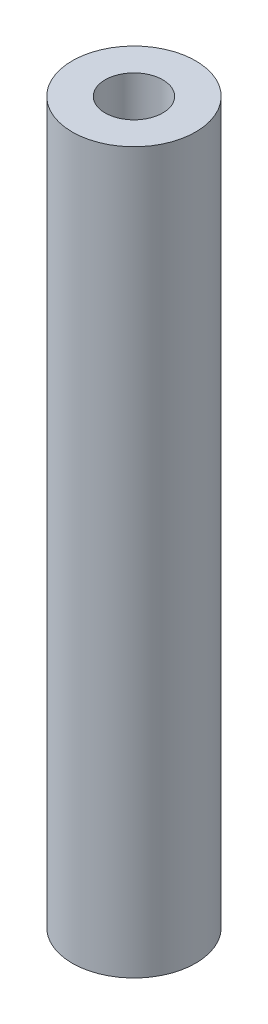
SolidWorks part; units mm, degrees
ref_plane "Front Plane" through (0, 0, 0) normal (0, 0, 1) x (1, 0, 0)
ref_plane "Top Plane" through (0, 0, 0) normal (0, 1, 0) x (1, 0, 0)
ref_plane "Right Plane" through (0, 0, 0) normal (1, 0, 0) x (0, 0, -1)
sketch "Sketch1" plane through (0, 0, 0) normal (0, 1, 0) x (1, 0, 0)
  circle A0 centre (0, 0) radius 3
  circle A1 centre (0, 0) radius 1.4
  dimension "D1" = 2.8
  dimension "D2" = 6
extrude "Extrusion" add sketch "Sketch1" along normal blind 35
